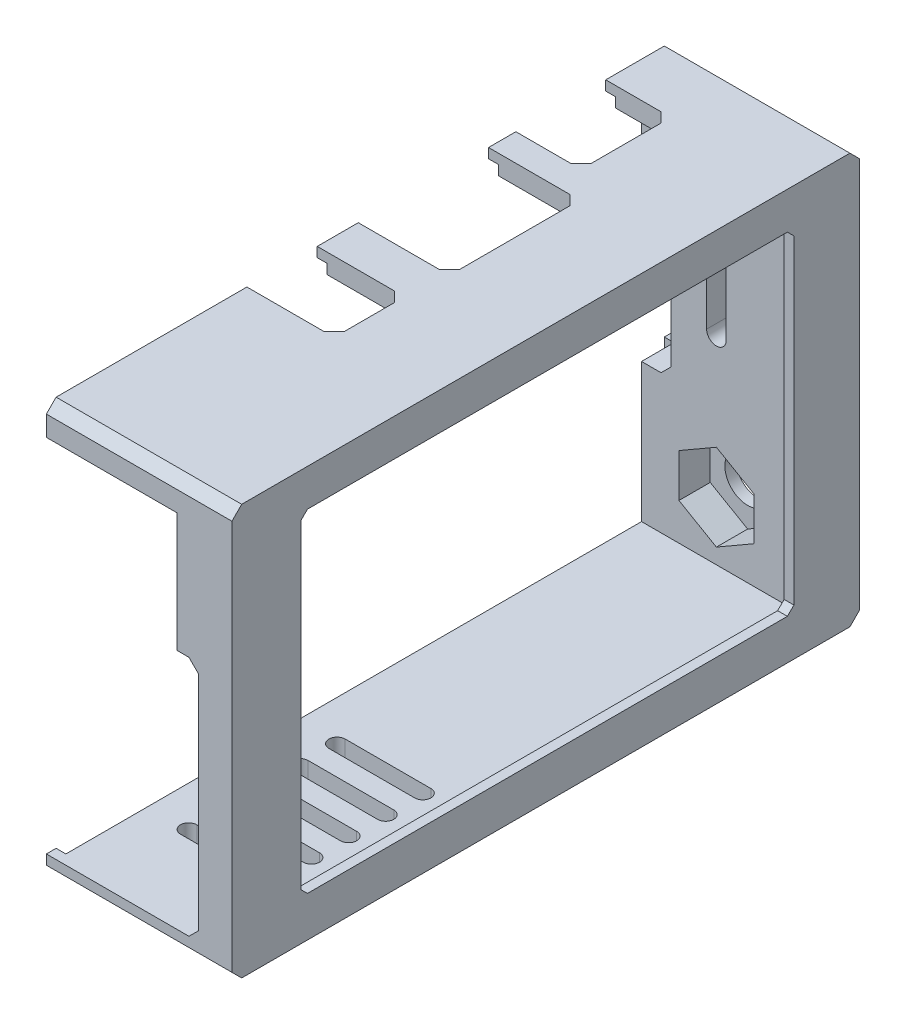
SolidWorks part; units mm, degrees
ref_plane "Front Plane" through (0, 0, 0) normal (0, 0, 1) x (1, 0, 0)
ref_plane "Top Plane" through (0, 0, 0) normal (0, 1, 0) x (1, 0, 0)
ref_plane "Right Plane" through (0, 0, 0) normal (1, 0, 0) x (0, 0, -1)
sketch "Sketch2" plane through (0, 0, 0) normal (1, 0, 0) x (0, 0, -1)
  line L1 (-37.9929, 28.829) -> (37.7071, 28.829)
  line L2 (-37.9929, 28.829) -> (-37.9929, -22.271)
  line L3 (-37.9929, -22.271) -> (37.7071, -22.271)
  line L4 (37.7071, 28.829) -> (37.7071, -22.271)
  line L5 (-45.3929, 31.329) -> (41.1071, 31.329)
  line L6 (-45.3929, 31.329) -> (-45.3929, -25.271)
  line L7 (-45.3929, -25.271) -> (41.1071, -25.271)
  line L8 (41.1071, 31.329) -> (41.1071, -25.271)
  line L9 (-45.5929, 31.529) -> (41.3071, 31.529)
  line L10 (-45.5929, 31.529) -> (-45.5929, -25.471)
  line L11 (-45.5929, -25.471) -> (41.3071, -25.471)
  line L12 (41.3071, 31.529) -> (41.3071, -25.471)
  line L13 (-48.5929, 34.529) -> (47.8071, 34.529)
  line L14 (-48.5929, 34.529) -> (-48.5929, -28.471)
  line L15 (-48.5929, -28.471) -> (47.8071, -28.471)
  line L16 (47.8071, 34.529) -> (47.8071, -28.471)
  dimension "D1" = 86.5
  dimension "D2" = 56.6
  dimension "D3" = 2.5
  dimension "D4" = 7.4
  dimension "D5" = 3.4
  dimension "D6" = 3
  dimension "D7" = 0.2
  dimension "D8" = 0.2
  dimension "D9" = 0.2
  dimension "D10" = 0.2
  dimension "D11" = 3
  dimension "D12" = 3
  dimension "D13" = 10.1
  dimension "D14" = 3
extrude "Boss-Extrude2" add sketch "Sketch2" against normal blind 1.5 contours L12 L9 L10 L11 L5 L8 L7 L6 | L8 L5 L6 L7 L1 L4 L3 L2 region at (0, 30.2953, 2.1429) region at (0, 31.4251, 2.1429)
extrude "Boss-Extrude3" add sketch "Sketch2<3>" against normal blind 27 contours L16 L13 L14 L15 L9 L12 L11 L10 region at (0, 33.3774, 0.3929)
sketch "Sketch2<3>" plane through (0, 0, 0) normal (1, 0, 0) x (0, 0, -1) same geometry as "Sketch2"
chamfer "Chamfer1" distance 1 angle 45 4 edges at (-0.75, -22.271, -37.7071) (-0.75, -22.271, 37.9929) (-0.75, 28.829, 37.9929) (-0.75, 28.829, -37.7071)
sketch "Sketch3" plane through (-27, 0, 0) normal (-1, 0, 0) x (0, 0, 1)
  line L1 (-47.8071, 34.529) -> (48.5929, 34.529)
  line L2 (-47.8071, 34.529) -> (-47.8071, -28.471)
  line L3 (-47.8071, -28.471) -> (48.5929, -28.471)
  line L4 (48.5929, 34.529) -> (48.5929, -28.471)
  line L5 (-46.3071, 33.029) -> (47.0929, 33.029)
  line L6 (-46.3071, 33.029) -> (-46.3071, -26.971)
  line L7 (-46.3071, -26.971) -> (47.0929, -26.971)
  line L8 (47.0929, 33.029) -> (47.0929, -26.971)
  dimension "D1" = 1.5
  dimension "D2" = 1.5
  dimension "D3" = 1.5
  dimension "D4" = 1.5
extrude "Boss-Extrude4" add sketch "Sketch3" along normal blind 1.5 contours L1 L4 L3 L2 | L7 L8 L5 L6
chamfer "Chamfer2" distance 1.5 angle 45 4 edges at (-14.25, -28.471, 48.5929) (-14.25, 34.529, 48.5929) (-14.25, -28.471, -47.8071) (-14.25, 34.529, -47.8071)
sketch "Sketch6" plane through (-28.5, 0, 0) normal (-1, 0, 0) x (0, 0, 1)
  line L0 (-46.3071, -25.471) -> (-46.3071, -4.171)
  line L1 (-46.3071, 33.029) -> (-46.3071, -26.971) construction
  line L2 (-46.3071, -4.171) -> (-41.3071, -4.171)
  line L3 (-41.3071, 31.529) -> (-41.3071, -25.471) construction
  line L4 (-41.3071, 31.529) -> (-41.3071, 9.829)
  line L5 (-41.3071, 31.529) -> (-41.3071, -25.471) construction
  line L7 (-41.3071, -4.171) -> (-51.0351, -4.171)
  line L8 (-41.3071, -4.171) -> (-41.3071, 9.829)
  line L9 (-41.3071, 9.829) -> (-51.0351, 9.829)
  line L10 (-51.0351, -4.171) -> (-51.0351, 9.829)
  line L11 (-46.3071, -26.971) -> (-46.3071, -25.471)
  dimension "D1" = 14
  dimension "D2" = 21.3
  dimension "D3" = 1.5
extrude "Cut-Extrude1" cut sketch "Sketch6" against normal blind 6 contours L8 L9 L10 L7
sketch "Sketch10" plane through (-28.5, 0, 0) normal (-1, 0, 0) x (0, 0, 1)
  line L0 (45.5929, -25.471) -> (45.5929, 11.629)
  line L1 (45.5929, 31.529) -> (45.5929, -25.471) construction
  line L2 (45.5929, 11.629) -> (48.5929, 11.629)
  line L3 (48.5929, 33.029) -> (48.5929, -26.971) construction
  line L4 (48.5929, 11.629) -> (48.5929, -25.471)
  line L5 (48.5929, -25.471) -> (45.5929, -25.471)
extrude "Cut-Extrude2" cut sketch "Sketch10" against normal blind 23.4 contours L4 L5 L0 L2
sketch "Sketch11" plane through (-28.5, 0, 0) normal (-1, 0, 0) x (0, 0, 1)
  line L2 (45.4829, 29.929) -> (48.5929, 29.929)
  line L3 (48.5929, 33.029) -> (48.5929, 11.629) construction
  line L4 (48.5929, 29.929) -> (48.5929, 11.629)
  line L5 (48.5929, 11.629) -> (45.4829, 11.629)
  line L10 (45.4829, 11.629) -> (45.4829, 29.929)
extrude "Cut-Extrude6" cut sketch "Sketch11" against normal blind 20.1
sketch "Sketch12" plane through (-28.5, 0, 0) normal (-1, 0, 0) x (0, 0, 1)
  line L2 (-46.3071, 34.529) -> (47.0929, 34.529) construction
  line L4 (-37.3101, 34.529) -> (-23.5101, 34.529)
  line L5 (-23.5101, 34.529) -> (-23.5101, 31.2959)
  line L6 (-23.5101, 31.2959) -> (-37.3101, 31.2959)
  line L7 (-37.3101, 31.2959) -> (-37.3101, 34.529)
extrude "Cut-Extrude7" cut sketch "Sketch12" against normal blind 10 contours L6 L7 L4 L5
sketch "Sketch13" plane through (-28.5, 0, 0) normal (-1, 0, 0) x (0, 0, 1)
  line L0 (-41.3122, 31.0125) -> (-19.3129, 31.0125)
  line L1 (-19.3129, 31.0125) -> (0.6878, 31.0125)
  line L2 (0.6878, 31.0125) -> (0.6878, 35.0582)
  line L3 (0.6878, 35.0582) -> (-19.3129, 35.0582)
  line L4 (-19.3129, 35.0582) -> (-19.3129, 31.0125)
extrude "Cut-Extrude8" cut sketch "Sketch13" against normal blind 14 contours L1 L2 L3 L4
sketch "Sketch15" plane through (-28.5, 0, 0) normal (-1, 0, 0) x (0, 0, 1)
  line L0 (-41.3067, 31.516) -> (6.9933, 31.516)
  line L1 (6.9933, 31.516) -> (17.7933, 31.516)
  line L2 (17.7933, 31.516) -> (17.7933, 35.1221)
  line L3 (17.7933, 35.1221) -> (6.9933, 35.1221)
  line L4 (6.9933, 35.1221) -> (6.9933, 31.516)
  dimension "D1" = 10.8
extrude "Cut-Extrude9" cut sketch "Sketch15" against normal blind 13.4 contours L1 L2 L3 L4
chamfer "Chamfer3" distance 1.5 angle 45 2 edges at (-18.5, 33.029, -37.3101) (-18.5, 33.029, -23.5101)
chamfer "Chamfer4" distance 1.5 angle 45 2 edges at (-14.5, 33.029, -19.3129) (-14.5, 33.029, 0.6878)
chamfer "Chamfer5" distance 1.5 angle 45 2 edges at (-15.1, 33.029, 6.9933) (-15.1, 33.029, 17.7933)
chamfer "Chamfer6" distance 1.5 angle 45 2 edges at (-22.5, 9.829, -44.5571) (-22.5, -4.171, -44.5571)
chamfer "Chamfer7" distance 1.5 angle 45 2 edges at (-5.1, -25.471, 47.0929) (-5.1, 11.629, 47.0929)
sketch "Sketch17" plane through (0, -28.471, 0) normal (0, -1, 0) x (1, 0, 0)
  line L0 (-20.83, 34.4126) -> (-7.67, 34.4126) construction
  line L1 (-20.83, 35.6626) -> (-7.67, 35.6626)
  line L2 (-20.83, 33.1626) -> (-7.67, 33.1626)
  line L3 (-7.67, 35.6626) -> (0, 35.6626)
  line L4 (0, 47.0929) -> (0, -46.3071) construction
  line L5 (-20.83, 35.6626) -> (-28.5, 35.6626)
  line L6 (-28.5, -46.3071) -> (-28.5, 47.0929) construction
  line L7 (-20.83, 28.7126) -> (-7.67, 28.7126) construction
  line L8 (-20.83, 29.9626) -> (-7.67, 29.9626)
  line L9 (-20.83, 27.4626) -> (-7.67, 27.4626)
  line L10 (-20.83, 23.0126) -> (-7.67, 23.0126) construction
  line L11 (-20.83, 24.2626) -> (-7.67, 24.2626)
  line L12 (-20.83, 21.7626) -> (-7.67, 21.7626)
  line L13 (-20.83, 17.3126) -> (-7.67, 17.3126) construction
  line L14 (-20.83, 18.5626) -> (-7.67, 18.5626)
  line L15 (-20.83, 16.0626) -> (-7.67, 16.0626)
  line L16 (-20.83, 11.6126) -> (-7.67, 11.6126) construction
  line L17 (-20.83, 12.8626) -> (-7.67, 12.8626)
  line L18 (-20.83, 10.3626) -> (-7.67, 10.3626)
  arc A0 (-20.83, 35.6626) -> (-20.83, 33.1626) centre (-20.83, 34.4126) ccw
  arc A1 (-7.67, 33.1626) -> (-7.67, 35.6626) centre (-7.67, 34.4126) ccw
  arc A2 (-20.83, 29.9626) -> (-20.83, 27.4626) centre (-20.83, 28.7126) ccw
  arc A3 (-7.67, 27.4626) -> (-7.67, 29.9626) centre (-7.67, 28.7126) ccw
  arc A4 (-20.83, 24.2626) -> (-20.83, 21.7626) centre (-20.83, 23.0126) ccw
  arc A5 (-7.67, 21.7626) -> (-7.67, 24.2626) centre (-7.67, 23.0126) ccw
  arc A6 (-20.83, 18.5626) -> (-20.83, 16.0626) centre (-20.83, 17.3126) ccw
  arc A7 (-7.67, 16.0626) -> (-7.67, 18.5626) centre (-7.67, 17.3126) ccw
  arc A8 (-20.83, 12.8626) -> (-20.83, 10.3626) centre (-20.83, 11.6126) ccw
  arc A9 (-7.67, 10.3626) -> (-7.67, 12.8626) centre (-7.67, 11.6126) ccw
  point P2 (-14.25, 34.4126)
  point P18 (-14.25, 28.7126)
  point P25 (-14.25, 23.0126)
  point P32 (-14.25, 17.3126)
  point P39 (-14.25, 11.6126)
  dimension "D1" = 5
extrude "Cut-Extrude11" cut sketch "Sketch17" against normal blind 4 contours L18 A9 L17 A8 | L15 A7 L14 A6 | L12 A5 L11 A4 | L9 A3 L8 A2 | L2 A1 L1 A0 region at (-14.25, -28.471, 34.4126) region at (-14.25, -28.471, 28.7126) region at (-14.25, -28.471, 23.0126) region at (-14.25, -28.471, 17.3126) region at (-14.25, -28.471, 11.6126)
sketch "Sketch18" plane through (0, 0, -47.8071) normal (0, 0, -1) x (-1, 0, 0)
  line L0 (15.5, 23.129) -> (15.5, 5.129) construction
  line L1 (17, 23.129) -> (17, 5.129)
  line L2 (14, 23.129) -> (14, 5.129)
  line L4 (22.5, -2.671) -> (22.5, 8.329) construction
  line L5 (0, 34.529) -> (28.5, 34.529) construction
  arc A0 (17, 23.129) -> (14, 23.129) centre (15.5, 23.129) ccw
  arc A1 (14, 5.129) -> (17, 5.129) centre (15.5, 5.129) ccw
  point P2 (15.5, 14.129)
  point P7 (15.5, 3.629)
  point P16 (15.5, 24.629)
  dimension "D1" = 5.5
  dimension "D2" = 9.9
  dimension "D3" = 3
  dimension "D4" = 21
extrude "Cut-Extrude12" cut sketch "Sketch18" against normal blind 8
sketch "Sketch19" plane through (0, 0, -47.8071) normal (0, 0, -1) x (-1, 0, 0)
  line L0 (15.5, -28.471) -> (15.5, -16.471)
  line L1 (28.5, -28.471) -> (0, -28.471) construction
  line L3 (28.5, -4.171) -> (28.5, -26.971) construction
  line L4 (31, -4.6218) -> (31, -29.3511)
  line L5 (0, -3.383) -> (0, -25.4916)
  line L6 (0, 33.029) -> (0, -26.971) construction
  line L7 (29.5, -16.471) -> (31, -16.471)
  line L8 (1.5, -16.471) -> (0, -16.471)
  line L9 (15.5, -23.111) -> (21.2504, -19.791)
  line L10 (21.2504, -19.791) -> (21.2504, -13.151)
  line L11 (21.2504, -13.151) -> (15.5, -9.831)
  line L12 (15.5, -9.831) -> (9.7496, -13.151)
  line L13 (9.7496, -13.151) -> (9.7496, -19.791)
  line L14 (9.7496, -19.791) -> (15.5, -23.111)
  circle A0 centre (15.5, -16.471) radius 14
  circle A1 centre (15.5, -16.471) radius 3.5
  circle A2 centre (15.5, -16.471) radius 5.7504 construction
  dimension "D3" = 28
  dimension "D1" = 13.28
  dimension "D2" = 12
  dimension "D4" = 2.5
  dimension "D5" = 11.5008
extrude "Cut-Extrude13" cut sketch "Sketch19" against normal blind 10 contours A1 region at (-13.0951, -14.0661, -47.8071)
sketch "Sketch21" plane through (0, 0, -41.3071) normal (0, 0, 1) x (1, 0, 0)
  line L1 (-15.5, -23.111) -> (-9.7496, -19.791)
  line L2 (-9.7496, -19.791) -> (-9.7496, -13.151)
  line L3 (-9.7496, -13.151) -> (-15.5, -9.831)
  line L4 (-15.5, -9.831) -> (-21.2504, -13.151)
  line L5 (-21.2504, -13.151) -> (-21.2504, -19.791)
  line L6 (-21.2504, -19.791) -> (-15.5, -23.111)
  circle A0 centre (-15.5, -16.471) radius 5.7504 construction
  dimension "D1" = 13.28
extrude "Cut-Extrude14" cut sketch "Sketch21" against normal blind 4.8
equation "\"D1@Sketch15\"=59.1-48.3"
equation "\"D1@Cut-Extrude9\"=1.5+11.9mm"
